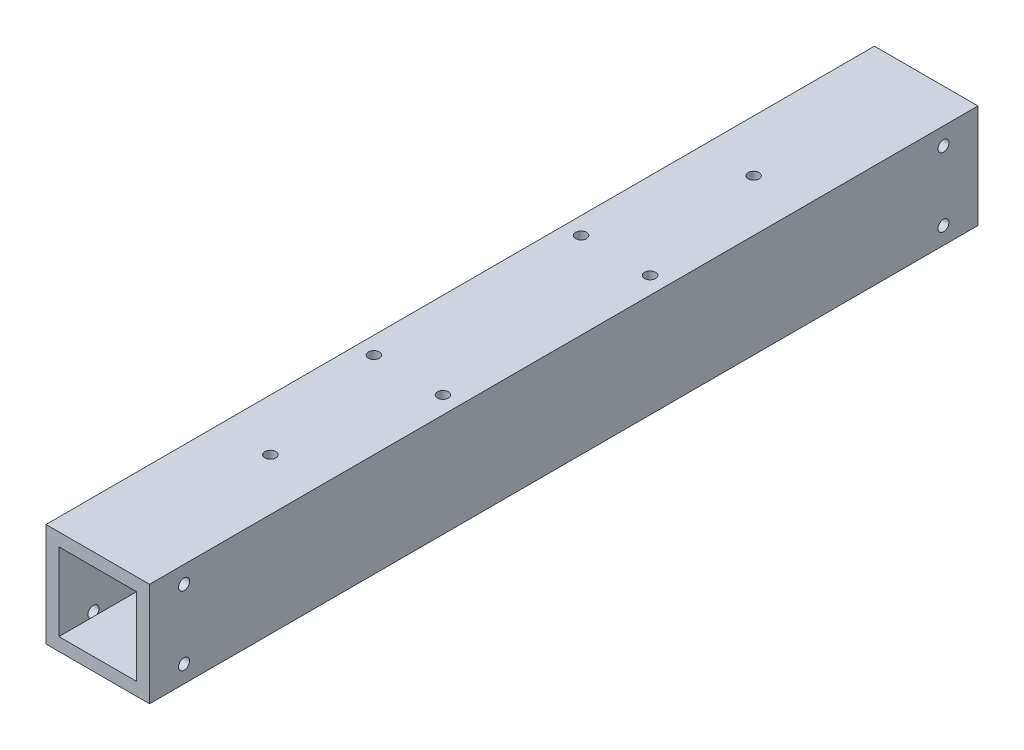
SolidWorks part; units mm, degrees
material "6061 Alloy"
ref_plane "Front Plane" through (0, 0, 0) normal (0, 0, 1) x (1, 0, 0)
ref_plane "Top Plane" through (0, 0, 0) normal (0, 1, 0) x (1, 0, 0)
ref_plane "Right Plane" through (0, 0, 0) normal (1, 0, 0) x (0, 0, -1)
sketch "Sketch1" plane through (0, 0, 0) normal (0, 1, 0) x (1, 0, 0)
  line L1 (-19.05, 152.4) -> (19.05, 152.4)
  line L2 (-19.05, 152.4) -> (-19.05, -152.4)
  line L3 (-19.05, -152.4) -> (19.05, -152.4)
  line L4 (19.05, 152.4) -> (19.05, -152.4)
  dimension "D1" = 19.05
  dimension "D2" = 19.05
  dimension "D3" = 152.4
  dimension "D4" = 152.4
extrude "Boss-Extrude1" add sketch "Sketch1" along normal mid plane 38.1
sketch "Sketch2" plane through (0, 0, 152.4) normal (0, 0, 1) x (1, 0, 0)
  line L0 (-19.05, 19.05) -> (-19.05, -19.05) construction
  line L1 (-14.2875, 14.2875) -> (14.2875, 14.2875)
  line L2 (-14.2875, 14.2875) -> (-14.2875, -14.2875)
  line L3 (-14.2875, -14.2875) -> (14.2875, -14.2875)
  line L4 (14.2875, 14.2875) -> (14.2875, -14.2875)
  line L5 (19.05, 19.05) -> (19.05, -19.05) construction
  line L6 (-19.05, -19.05) -> (19.05, -19.05) construction
  line L7 (-19.05, 19.05) -> (19.05, 19.05) construction
  dimension "D1" = 4.7625
  dimension "D2" = 4.7625
  dimension "D3" = 4.7625
  dimension "D4" = 4.7625
extrude "Cut-Extrude1" cut sketch "Sketch2" against normal through all
hole_wizard "#10-32 Tapped Hole1" positions "Sketch4" profile "Sketch3" tap size "#10-32" standard "ANSI Inch" end condition up to next
sketch "Sketch4" plane through (19.05, 0, 0) normal (1, 0, 0) x (0, 0, -1)
  line L0 (-152.4, 19.05) -> (-152.4, -19.05) construction
  point P0 (-139.7, 12.7)
  point P2 (-139.7, -12.7)
  dimension "D1" = 12.7
  dimension "D2" = 12.7
  dimension "D3" = 12.7
sketch "Sketch3" plane through (19.05, 12.7, 139.7) normal (0, 1, 0) x (0, 0, -1)
  line L0 (0, 0) -> (0, 4.7635)
  line L1 (0, 4.7635) -> (2.0193, 4.7635)
  line L2 (2.0193, 4.7635) -> (2.0193, 0)
  line L5 (2.0193, 0) -> (0, 0)
  line L11 (0, -6.35) -> (0, 107.95) construction
  dimension "Thru Tap Drill Dia." = 4.0386
  dimension "Thru Tap Drill Depth" = 4.7635
cosmetic thread "Hole Thread1" parameters "D2"=4.826
cosmetic thread "Hole Thread2" parameters "D2"=4.826
hole_wizard "#10-32 Tapped Hole2" positions "Sketch6" profile "Sketch5" tap size "#10-32" standard "ANSI Inch" end condition up to next
sketch "Sketch6" plane through (0, 19.05, 0) normal (0, 1, 0) x (1, 0, 0)
  point P0 (-12.7, -38.1)
  point P2 (12.7, -38.1)
  dimension "D1" = 12.7
  dimension "D2" = 12.7
  dimension "D3" = 38.1
sketch "Sketch5" plane through (-12.7, 19.05, 38.1) normal (1, 0, 0) x (0, 0, 1)
  line L0 (0, 0) -> (0, 4.7635)
  line L1 (0, 4.7635) -> (2.0193, 4.7635)
  line L2 (2.0193, 4.7635) -> (2.0193, 0)
  line L5 (2.0193, 0) -> (0, 0)
  line L11 (0, -6.35) -> (0, 107.95) construction
  dimension "Thru Tap Drill Dia." = 4.0386
  dimension "Thru Tap Drill Depth" = 4.7635
cosmetic thread "Hole Thread3" parameters "D2"=4.826
cosmetic thread "Hole Thread4" parameters "D2"=4.826
mirror "Mirror1" about plane through (0, 0, 0) normal (1, 0, 0) of "#10-32 Tapped Hole1"
mirror "Mirror3" about plane through (0, 0, 0) normal (0, 1, 0) of "#10-32 Tapped Hole2"
mirror "Mirror4" about plane through (0, 0, 0) normal (0, 0, 1) of "Mirror3", "Mirror1", "#10-32 Tapped Hole2", "#10-32 Tapped Hole1"
hole_wizard "#10-32 Tapped Hole3" positions "Sketch10" profile "Sketch9" tap size "#10-32" standard "ANSI Inch" end condition up to next
sketch "Sketch10" plane through (0, 19.05, 0) normal (0, 1, 0) x (1, 0, 0)
  point P0 (0, -88.9)
  point P4 (0, 88.9)
  dimension "D1" = 88.9
  dimension "D2" = 88.9
sketch "Sketch9" plane through (0, 19.05, 88.9) normal (1, 0, 0) x (0, 0, 1)
  line L0 (0, 0) -> (0, 38.1)
  line L1 (0, 38.1) -> (2.0193, 38.1)
  line L2 (2.0193, 38.1) -> (2.0193, 0)
  line L5 (2.0193, 0) -> (0, 0)
  line L11 (0, -6.35) -> (0, 107.95) construction
  dimension "Thru Tap Drill Dia." = 4.0386
  dimension "Thru Tap Drill Depth" = 38.1
cosmetic thread "Hole Thread5" parameters "D2"=4.826
cosmetic thread "Hole Thread6" parameters "D2"=4.826
mirror "Mirror5" about plane through (0, 0, 0) normal (0, 1, 0) of "#10-32 Tapped Hole3"
hole_wizard "3/32 (0.09375) Diameter Hole3" positions "Sketch12" profile "Sketch11" hole size "3/32" standard "ANSI Inch"
sketch "Sketch12" plane through (0, -19.05, 0) normal (0, -1, 0) x (-1, 0, 0)
  point P0 (0, -63.5)
  point P6 (-15.875, 63.5)
  point P8 (15.875, 63.5)
  dimension "D1" = 63.5
  dimension "D2" = 63.5
  dimension "D3" = 15.875
  dimension "D4" = 15.875
sketch "Sketch11" plane through (0, -19.05, 63.5) normal (1, 0, 0) x (0, 0, -1)
  line L0 (0, 0) -> (0, 1.906)
  line L1 (0, 1.906) -> (1.1906, 1.1906)
  line L2 (1.1906, 1.1906) -> (1.1906, 0)
  line L5 (1.1906, 0) -> (0, 0)
  line L10 (0, 1.906) -> (-1.1906, 1.1906) construction
  line L11 (0, -6.35) -> (0, 107.95) construction
  dimension "Hole Dia." = 2.3812
  dimension "Hole Depth" = 1.1906
  dimension "Drill Angle" = 118
sketch "Sketch13" plane through (0, -19.05, 0) normal (0, -1, 0) x (1, 0, 0)
  line L0 (10.4175, -4.1814) -> (8.83, -6.9311)
  line L1 (-1.5875, 7.9375) -> (1.5875, 7.9375)
  line L2 (-1.5875, 7.9375) -> (-1.5875, 11.1125)
  line L3 (-1.5875, 11.1125) -> (1.5875, 11.1125)
  line L4 (1.5875, 7.9375) -> (1.5875, 11.1125)
  line L5 (-1.5875, 7.9375) -> (1.5875, 11.1125) construction
  line L6 (-1.5875, 11.1125) -> (1.5875, 7.9375) construction
  line L7 (7.6678, -2.5939) -> (10.4175, -4.1814)
  line L8 (6.0803, -5.3436) -> (8.83, -6.9311)
  line L9 (7.6678, -2.5939) -> (6.0803, -5.3436)
  line L10 (-8.83, -6.9311) -> (-10.4175, -4.1814)
  line L11 (-6.0803, -5.3436) -> (-8.83, -6.9311)
  line L12 (-7.6678, -2.5939) -> (-10.4175, -4.1814)
  line L13 (-6.0803, -5.3436) -> (-7.6678, -2.5939)
  circle A0 centre (0, 0) radius 9.525
  circle A1 centre (0, 0) radius 9.525
  circle A2 centre (0, 0) radius 9.525
  circle A3 centre (-1.5875, 11.1125) radius 0.7937
  circle A4 centre (1.5875, 11.1125) radius 0.7938
  circle A5 centre (1.5875, 7.9375) radius 0.7937
  circle A6 centre (-1.5875, 7.9375) radius 0.7938
  circle A7 centre (10.4175, -4.1814) radius 0.7938
  circle A8 centre (7.6678, -2.5939) radius 0.7937
  circle A9 centre (6.0803, -5.3436) radius 0.7937
  circle A10 centre (8.83, -6.9311) radius 0.7938
  circle A11 centre (-8.83, -6.9311) radius 0.7938
  circle A12 centre (-6.0803, -5.3436) radius 0.7938
  circle A13 centre (-7.6678, -2.5939) radius 0.7937
  circle A14 centre (-10.4175, -4.1814) radius 0.7937
  point P3 (0, 9.525)
  point P21 (0, 0)
  point P29 (0, 9.525)
  point P45 (0, 0)
  dimension "D1" = 3.175
  dimension "D4" = 4
  dimension "D2" = 3.175
  dimension "D3" = 3
  dimension "D5" = 3
extrude "Cut-Extrude2" cut sketch "Sketch13" against normal blind 1.5875 contours A0 L4 L3 L2 | L12 A0 L11 L13 | A0 L12 L10 L11 | L8 A0 L7 L9 | A0 L8 L0 L7 | L1 A5 L4 | L4 A5 L1 | L4 A4 L3 | L3 A4 L4 | L3 A3 L2 | L2 A3 L3 | L12 A14 L10 | L10 A14 L12 | L10 A11 L11 | L11 A11 L10 | L11 A12 L13 | L13 A12 L11 | L12 A13 L13 | L13 A13 L12 | L0 A10 L8 | L9 A9 L8 | L8 A9 L9 | L7 A8 L9 | L9 A8 L7 | L7 A7 L0 | A6 L1 A5 L4 A0 L2 | A6 | A10 | A7 | L2 L1 L4 L3 region at (9.9573, -19.05, -4.3047) region at (8.8187, -19.05, -5.0915) region at (8.7067, -19.05, -6.4709) region at (7.6382, -19.05, -4.4099) region at (7.7911, -19.05, -3.0541) region at (7.6267, -19.05, -2.4405) region at (5.9269, -19.05, -5.3847) region at (6.5405, -19.05, -5.2203) region at (-7.6382, -19.05, -4.4099) region at (-8.8187, -19.05, -5.0915) region at (0, -19.05, 10.1829) region at (0, -19.05, 8.8198) region at (-6.5405, -19.05, -5.2203) region at (-5.9269, -19.05, -5.3847) region at (-8.8711, -19.05, -7.0845) region at (-8.7067, -19.05, -6.4709) region at (1.6998, -19.05, 7.8252) region at (1.2506, -19.05, 8.2744) region at (1.2506, -19.05, 10.7756) region at (1.6998, -19.05, 11.2248) region at (-7.6267, -19.05, -2.4405) region at (-7.7911, -19.05, -3.0541) region at (-9.9573, -19.05, -4.3047) region at (-10.5709, -19.05, -4.1403) region at (-1.6998, -19.05, 11.2248) region at (-1.2506, -19.05, 10.7756)
hole_wizard "#6-32 Tapped Hole1" positions "Sketch14" profile "Sketch16" tap size "#6-32" standard "ANSI Inch" end condition up to next
sketch "Sketch14" plane through (0, -19.05, 0) normal (0, -1, 0) x (-1, 0, 0)
  point P0 (0, 7.9375)
  point P9 (6.8741, -3.9687)
  point P10 (-6.8741, -3.9688)
  dimension "D1" = 7.9375
  dimension "D2" = 3
sketch "Sketch16" plane through (0, -19.05, -7.9375) normal (1, 0, 0) x (0, 0, -1)
  line L0 (0, 0) -> (0, 4.7625)
  line L1 (0, 4.7625) -> (1.3525, 4.7625)
  line L2 (1.3525, 4.7625) -> (1.3525, 0)
  line L5 (1.3525, 0) -> (0, 0)
  line L11 (0, -6.35) -> (0, 107.95) construction
  dimension "Thru Tap Drill Dia." = 2.7051
  dimension "Thru Tap Drill Depth" = 4.7625
cosmetic thread "Hole Thread7" parameters "D2"=3.5052
cosmetic thread "Hole Thread8" parameters "D2"=3.5052
cosmetic thread "Hole Thread9" parameters "D2"=3.5052
